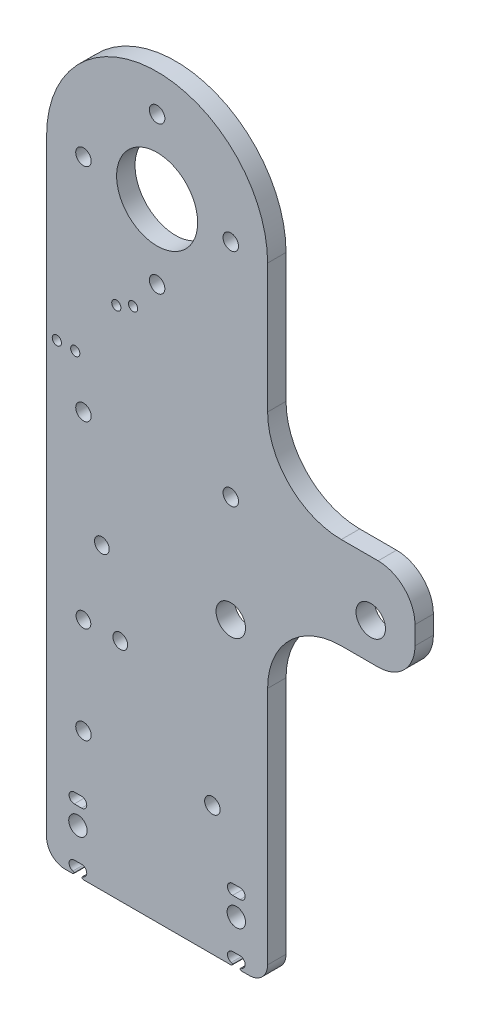
SolidWorks part; units mm, degrees
material "6061 Alloy"
ref_plane "Front Plane" through (0, 0, 0) normal (0, 0, 1) x (1, 0, 0)
ref_plane "Top Plane" through (0, 0, 0) normal (0, 1, 0) x (1, 0, 0)
ref_plane "Right Plane" through (0, 0, 0) normal (1, 0, 0) x (0, 0, -1)
sketch "Sketch1" plane through (0, 0, 0) normal (0, 0, 1) x (1, 0, 0)
  line L0 (20.5, -63) -> (22.5, -63) construction
  line L5 (0, 65) -> (0, -15) construction
  line L6 (-30, 0) -> (30, 0) construction
  line L11 (0, 6.5) -> (0, -24.5) construction
  line L14 (20.5, -61.6) -> (22.5, -61.6)
  line L20 (22.5, -47) -> (20.5, -47) construction
  line L23 (0, -15) -> (0, 105) construction
  line L24 (-30, -65) -> (-30, 105)
  line L25 (30, -65) -> (30, 105)
  line L26 (-30, -65) -> (30, -65)
  line L27 (22.5, -48.4) -> (20.5, -48.4)
  line L28 (22.5, -45.6) -> (20.5, -45.6)
  line L29 (-20.5, -64.4) -> (-20.5, -65)
  line L31 (20.5, -64.4) -> (20.5, -65)
  line L32 (20.5, -65) -> (22.5, -65)
  line L33 (22.5, -64.4) -> (22.5, -65)
  line L34 (-22.5, -64.4) -> (-22.5, -65)
  line L35 (-20.5, -61.6) -> (-22.5, -61.6)
  line L36 (-22.5, -47) -> (-20.5, -47) construction
  line L37 (-22.5, -48.4) -> (-20.5, -48.4)
  line L38 (-22.5, -45.6) -> (-20.5, -45.6)
  circle A6 centre (0, 105) radius 11
  arc A18 (30, 105) -> (-30, 105) centre (0, 105) ccw
  circle A19 centre (0, 105) radius 20 construction
  circle A20 centre (0, 125) radius 2.1
  circle A21 centre (20, 105) radius 2.1
  circle A22 centre (0, 85) radius 2.1
  circle A23 centre (-20, 105) radius 2.1
  circle A24 centre (-6.5104, 76.583) radius 1.25
  circle A25 centre (-22.2229, 58.2223) radius 1.25
  circle A26 centre (-27.2229, 58.2223) radius 1.25
  circle A27 centre (-11.0761, 74.5449) radius 1.25
  arc A28 (20.5, -61.6) -> (20.5, -64.4) centre (20.5, -63) ccw
  arc A29 (22.5, -64.4) -> (22.5, -61.6) centre (22.5, -63) ccw
  arc A30 (22.5, -48.4) -> (22.5, -45.6) centre (22.5, -47) ccw
  arc A31 (20.5, -45.6) -> (20.5, -48.4) centre (20.5, -47) ccw
  circle A32 centre (21.5, -53) radius 2.5
  arc A33 (-22.5, -64.4) -> (-22.5, -61.6) centre (-22.5, -63) cw
  arc A34 (-20.5, -61.6) -> (-20.5, -64.4) centre (-20.5, -63) cw
  circle A35 centre (-21.5, -53) radius 2.5
  arc A36 (-22.5, -48.4) -> (-22.5, -45.6) centre (-22.5, -47) cw
  arc A37 (-20.5, -45.6) -> (-20.5, -48.4) centre (-20.5, -47) cw
  point P0 (0, 0)
  point P1 (0, -5)
  point P16 (21.5, -63)
  point P21 (21.5, -47)
  point P52 (0, 105)
  point P56 (-21.5, -47)
  dimension "D4" = 5
  dimension "D5" = 5
  dimension "D8" = 22
  dimension "D3" = 2.5
  dimension "D7" = 2.5
  dimension "D14" = 4.2
  dimension "D2" = 30
  dimension "D13" = 40
  dimension "D10" = 1.4
  dimension "D11" = 5
  dimension "D6" = 170
  dimension "D9" = 120
  dimension "D15" = 4
extrude "Boss-Extrude1" add sketch "Sketch1" along normal mid plane 5
sketch "Sketch15" plane through (0, 0, -2.5) normal (0, 0, -1) x (-1, 0, 0)
  line L0 (30, -65) -> (22.5, -65) construction
  line L1 (-30, -65) -> (-30, 105) construction
  line L2 (30, -65) -> (30, 105) construction
  circle A0 centre (20, -30) radius 2.1
  circle A1 centre (-15, -30) radius 2.1
  circle A3 centre (-20, 45) radius 2.1
  circle A4 centre (20, 45) radius 2.1
  dimension "D5" = 4.2
  dimension "D1" = 10
  dimension "D2" = 45
  dimension "D3" = 10
  dimension "D4" = 0
  dimension "D6" = 35
  dimension "D7" = 75
extrude "Cut-Extrude15" cut sketch "Sketch15" against normal up to next
extrude "Cut-Extrude20" [suppressed] cut sketch "Sketch20" against normal through all
sketch "Sketch20" plane through (-484.848, 103.0873, 2.5) normal (0, 0, 1) x (0, -1, 0)
  line L1 (150.0873, 505.348) -> (150.0873, 507.348) construction
  line L2 (148.9873, 505.348) -> (148.9873, 507.348)
  line L3 (151.1873, 505.348) -> (151.1873, 507.348)
  line L4 (166.0873, 505.348) -> (166.0873, 507.348) construction
  line L5 (164.9873, 505.348) -> (164.9873, 507.348)
  line L6 (167.1873, 505.348) -> (167.1873, 507.348)
  line L7 (166.0873, 462.348) -> (166.0873, 464.348) construction
  line L8 (164.9873, 462.348) -> (164.9873, 464.348)
  line L9 (167.1873, 462.348) -> (167.1873, 464.348)
  line L10 (150.0873, 462.348) -> (150.0873, 464.348) construction
  line L11 (148.9873, 462.348) -> (148.9873, 464.348)
  line L12 (151.1873, 462.348) -> (151.1873, 464.348)
  circle A0 centre (156.0873, 506.348) radius 2.5
  circle A1 centre (156.0873, 463.348) radius 2.5
  arc A2 (148.9873, 505.348) -> (151.1873, 505.348) centre (150.0873, 505.348) ccw
  arc A3 (151.1873, 507.348) -> (148.9873, 507.348) centre (150.0873, 507.348) ccw
  arc A4 (164.9873, 505.348) -> (167.1873, 505.348) centre (166.0873, 505.348) ccw
  arc A5 (167.1873, 507.348) -> (164.9873, 507.348) centre (166.0873, 507.348) ccw
  arc A6 (164.9873, 462.348) -> (167.1873, 462.348) centre (166.0873, 462.348) ccw
  arc A7 (167.1873, 464.348) -> (164.9873, 464.348) centre (166.0873, 464.348) ccw
  arc A8 (148.9873, 462.348) -> (151.1873, 462.348) centre (150.0873, 462.348) ccw
  arc A9 (151.1873, 464.348) -> (148.9873, 464.348) centre (150.0873, 464.348) ccw
  point P10 (150.0873, 506.348)
  point P15 (166.0873, 506.348)
  point P24 (166.0873, 463.348)
  point P33 (150.0873, 463.348)
fillet "Fillet1" radius 5 2 edges at (-30, -65, 0) (30, -65, 0)
fillet "Fillet2" radius 0.5 8 edges at (22.5, -65, 0) (22.5, -64.4, 0) (20.5, -64.4, 0) (20.5, -65, 0) (-20.5, -64.4, 0) (-20.5, -65, 0) (-22.5, -64.4, 0) (-22.5, -65, 0)
sketch "Sketch21" plane through (0, 0, 2.5) normal (0, 0, 1) x (1, 0, 0)
  line L0 (-30, -60) -> (-30, 105) construction
  line L1 (30, -60) -> (30, 105) construction
  circle A0 centre (-20, -3.8406) radius 2
  circle A1 centre (-10, -3.8406) radius 2
  circle A2 centre (-15, 16.1594) radius 2
  circle A3 centre (20, 16.1594) radius 4
  dimension "D1" = 4
  dimension "D2" = 10
  dimension "D3" = 10
  dimension "D4" = 20
  dimension "D5" = 5
  dimension "D6" = 8
  dimension "D7" = 10
  dimension "D8" = 20
extrude "Cut-Extrude21" cut sketch "Sketch21" against normal through all
sketch "Sketch22" plane through (0, 0, 2.5) normal (0, 0, 1) x (1, 0, 0)
  line L0 (30, 25) -> (70, 25)
  line L1 (70, 25) -> (70, 50)
  line L2 (70, 50) -> (30, 50)
  line L3 (30, -60) -> (30, 105) construction
  circle A1 centre (58, 35) radius 4
  arc M17 (30, 105) -> (-30, 105) centre (0, 105) ccw
  dimension "D3" = 8
  dimension "D4" = 10
  dimension "D5" = 12
  dimension "D1" = 90
  dimension "D2" = 40
  dimension "D6" = 25
  dimension "D7" = 25
extrude "Boss-Extrude2" add sketch "Sketch22" against normal blind 5 contours L1 L2 L0 A1 M17
fillet "Fillet10" radius 20 2 edges at (30, 50, 0) (30, 25, 0)
fillet "Fillet11" radius 10 2 edges at (70, 50, 0) (70, 25, 0)
